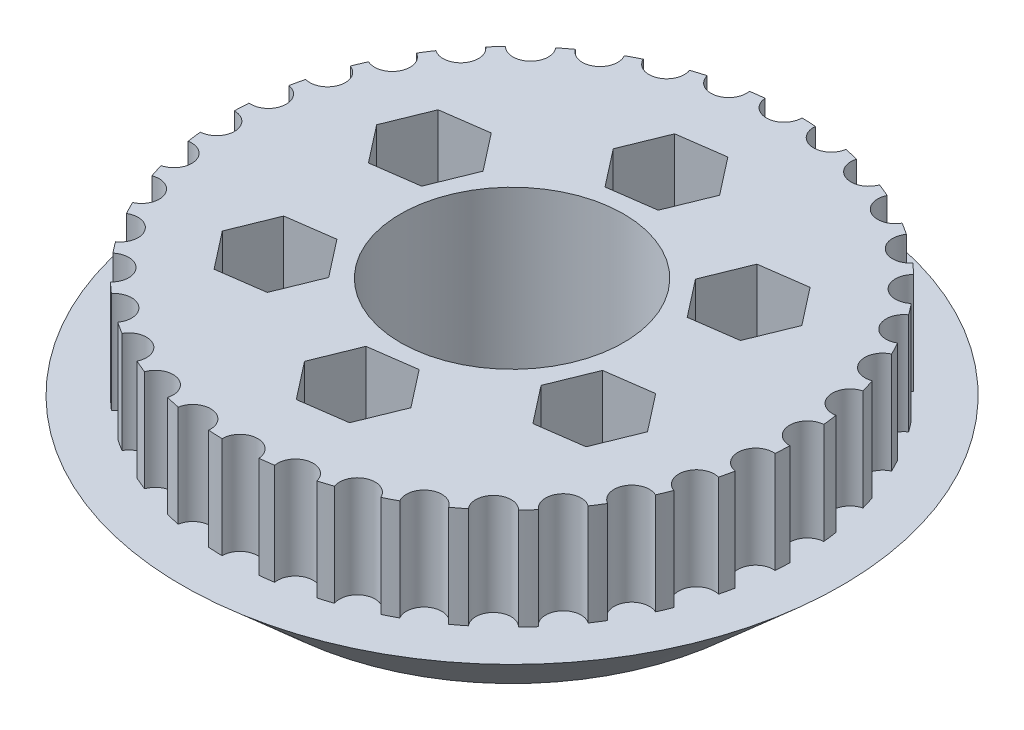
SolidWorks part; units mm, degrees
ref_plane "Front Plane" through (0, 0, 0) normal (0, 0, 1) x (1, 0, 0)
ref_plane "Top Plane" through (0, 0, 0) normal (0, 1, 0) x (1, 0, 0)
ref_plane "Right Plane" through (0, 0, 0) normal (1, 0, 0) x (0, 0, -1)
sketch "Sketch1" plane through (0, 0, 0) normal (0, 1, 0) x (1, 0, 0)
  circle A0 centre (0, 0) radius 28
  circle A1 centre (0, 0) radius 16.75 construction
  circle A2 centre (0, 0) radius 11
  circle A3 centre (-1.4643, 16.6859) radius 2.75
  circle A4 centre (13.7182, 9.611) radius 2.75
  circle A5 centre (15.1825, -7.0748) radius 2.75
  circle A6 centre (1.4643, -16.6859) radius 2.75
  circle A7 centre (-13.7182, -9.611) radius 2.75
  circle A8 centre (-15.1825, 7.0748) radius 2.75
  circle A9 centre (-24.8012, 12.9961) radius 1.75
  circle A10 centre (-22.1677, 17.1054) radius 1.75
  circle A11 centre (-18.8606, 20.6949) radius 1.75
  circle A12 centre (-14.9804, 23.6556) radius 1.75
  circle A13 centre (-10.6451, 25.8975) radius 1.75
  circle A14 centre (-5.9863, 27.3526) radius 1.75
  circle A15 centre (-1.1456, 27.9766) radius 1.75
  circle A16 centre (3.7298, 27.7505) radius 1.75
  circle A17 centre (8.492, 26.6812) radius 1.75
  circle A18 centre (12.9961, 24.8012) radius 1.75
  circle A19 centre (17.1054, 22.1677) radius 1.75
  circle A20 centre (20.6949, 18.8606) radius 1.75
  circle A21 centre (23.6556, 14.9804) radius 1.75
  circle A22 centre (25.8975, 10.6451) radius 1.75
  circle A23 centre (27.3526, 5.9863) radius 1.75
  circle A24 centre (27.9766, 1.1456) radius 1.75
  circle A25 centre (27.7505, -3.7298) radius 1.75
  circle A26 centre (26.6812, -8.492) radius 1.75
  circle A27 centre (24.8012, -12.9961) radius 1.75
  circle A28 centre (22.1677, -17.1054) radius 1.75
  circle A29 centre (18.8606, -20.6949) radius 1.75
  circle A30 centre (14.9804, -23.6556) radius 1.75
  circle A31 centre (10.6451, -25.8975) radius 1.75
  circle A32 centre (5.9863, -27.3526) radius 1.75
  circle A33 centre (1.1456, -27.9766) radius 1.75
  circle A34 centre (-3.7298, -27.7505) radius 1.75
  circle A35 centre (-8.492, -26.6812) radius 1.75
  circle A36 centre (-12.9961, -24.8012) radius 1.75
  circle A37 centre (-17.1054, -22.1677) radius 1.75
  circle A38 centre (-20.6949, -18.8606) radius 1.75
  circle A39 centre (-23.6556, -14.9804) radius 1.75
  circle A40 centre (-25.8975, -10.6451) radius 1.75
  circle A41 centre (-27.3526, -5.9863) radius 1.75
  circle A42 centre (-27.9766, -1.1456) radius 1.75
  circle A43 centre (-27.7505, 3.7298) radius 1.75
  circle A44 centre (-26.6812, 8.492) radius 1.75
  circle A45 centre (0, 0) radius 23 construction
  circle A46 centre (0, 0) radius 20 construction
  dimension "D1" = 56
  dimension "D2" = 22
  dimension "D3" = 33.5
  dimension "D4" = 5.5
  dimension "D6" = 3.5
  dimension "D8" = 46
  dimension "D9" = 40
  dimension "D5" = 6
  dimension "D7" = 36
extrude "Boss-Extrude1" add sketch "Sketch1" along normal blind 10 contours A44 A0 A43 A42 A41 A40 A39 A38 A37 A36 A35 A34 A33 A32 A31 A30 A29 A28 A27 A26 A25 A24 A23 A22 A21 A20 A19 | A7 | A8 | A3 | A4 | A5 | A6 region at (25.4369, 0, -1.0416) region at (-1.4643, 0, -16.6859) region at (13.7182, 0, -9.611) region at (15.1825, 0, 7.0748) region at (1.4643, 0, 16.6859) region at (-13.7182, 0, 9.611) region at (-15.1825, 0, -7.0748)
sketch "Sketch2" plane through (0, 0, 0) normal (0, -1, 0) x (1, 0, 0)
  circle A1 centre (0, 0) radius 32.5
  circle A2 centre (0, 0) radius 11
  dimension "D1" = 65
  dimension "D2" = 22
sketch "Sketch4" plane through (0, 10, 0) normal (0, 1, 0) x (1, 0, 0)
  line L0 (-10.5768, 7.7153) -> (-13.4343, 11.3837)
  line L1 (-18.3239, -10.2515) -> (-15.4664, -13.9199)
  line L2 (-15.4664, -13.9199) -> (-10.8608, -13.2795)
  line L3 (-10.8608, -13.2795) -> (-9.1126, -8.9706)
  line L4 (-9.1126, -8.9706) -> (-11.9701, -5.3022)
  line L5 (-11.9701, -5.3022) -> (-16.5757, -5.9426)
  line L6 (-16.5757, -5.9426) -> (-18.3239, -10.2515)
  line L7 (-12.325, 3.4064) -> (-10.5768, 7.7153)
  line L8 (-16.9307, 2.766) -> (-12.325, 3.4064)
  line L9 (-19.7882, 6.4344) -> (-16.9307, 2.766)
  line L10 (-18.04, 10.7432) -> (-19.7882, 6.4344)
  line L11 (-13.4343, 11.3837) -> (-18.04, 10.7432)
  line L12 (1.3932, 13.0175) -> (3.1414, 17.3263)
  line L13 (-3.2125, 12.377) -> (1.3932, 13.0175)
  line L14 (-6.07, 16.0454) -> (-3.2125, 12.377)
  line L15 (-4.3218, 20.3543) -> (-6.07, 16.0454)
  line L16 (0.2839, 20.9947) -> (-4.3218, 20.3543)
  line L17 (3.1414, 17.3263) -> (0.2839, 20.9947)
  line L18 (11.9701, 5.3022) -> (16.5757, 5.9426)
  line L19 (9.1126, 8.9706) -> (11.9701, 5.3022)
  line L20 (10.8608, 13.2795) -> (9.1126, 8.9706)
  line L21 (15.4664, 13.9199) -> (10.8608, 13.2795)
  line L22 (18.3239, 10.2515) -> (15.4664, 13.9199)
  line L23 (16.5757, 5.9426) -> (18.3239, 10.2515)
  line L24 (10.5768, -7.7153) -> (13.4343, -11.3837)
  line L25 (12.325, -3.4064) -> (10.5768, -7.7153)
  line L26 (16.9307, -2.766) -> (12.325, -3.4064)
  line L27 (19.7882, -6.4344) -> (16.9307, -2.766)
  line L28 (18.04, -10.7432) -> (19.7882, -6.4344)
  line L29 (13.4343, -11.3837) -> (18.04, -10.7432)
  line L30 (-1.3932, -13.0175) -> (-3.1414, -17.3263)
  line L31 (3.2125, -12.377) -> (-1.3932, -13.0175)
  line L32 (6.07, -16.0454) -> (3.2125, -12.377)
  line L33 (4.3218, -20.3543) -> (6.07, -16.0454)
  line L34 (-0.2839, -20.9947) -> (4.3218, -20.3543)
  line L35 (-3.1414, -17.3263) -> (-0.2839, -20.9947)
  circle A0 centre (-13.7182, -9.611) radius 4.027 construction
  dimension "D1" = 4.65
  dimension "D2" = 6
ref_plane "Plane1" through (0, -8, 0) normal (0, -1, 0) x (-1, 0, 0)
sketch "Sketch3" plane through (0, -8, 0) normal (0, -1, 0) x (-1, 0, 0)
  circle A0 centre (0, 0) radius 23.5
  circle A1 centre (0, 0) radius 11
  dimension "D1" = 22
  dimension "D2" = 47
loft "Loft2" add section "Sketch2" section "Sketch3" connector at (1.5106, 0, 32.4649) connector at (0.0886, -8, 23.4998)
extrude "Cut-Extrude1" cut sketch "Sketch3<4>" against normal through all both and the other way through all contours A1 region at (0, -8, 0)
sketch "Sketch3<4>" plane through (0, -8, 0) normal (0, -1, 0) x (-1, 0, 0) same geometry as "Sketch3"
extrude "Cut-Extrude2" cut sketch "Sketch4" against normal blind 13
extrude "Cut-Extrude3" cut sketch "Sketch1<7>" against normal through all contours A5 | A6 | A7 | A8 | A3 | A4 region at (-1.4643, 0, -16.6859) region at (13.7182, 0, -9.611) region at (15.1825, 0, 7.0748) region at (1.4643, 0, 16.6859) region at (-13.7182, 0, 9.611) region at (-15.1825, 0, -7.0748)
sketch "Sketch1<7>" plane through (0, 0, 0) normal (0, 1, 0) x (1, 0, 0) same geometry as "Sketch1"
